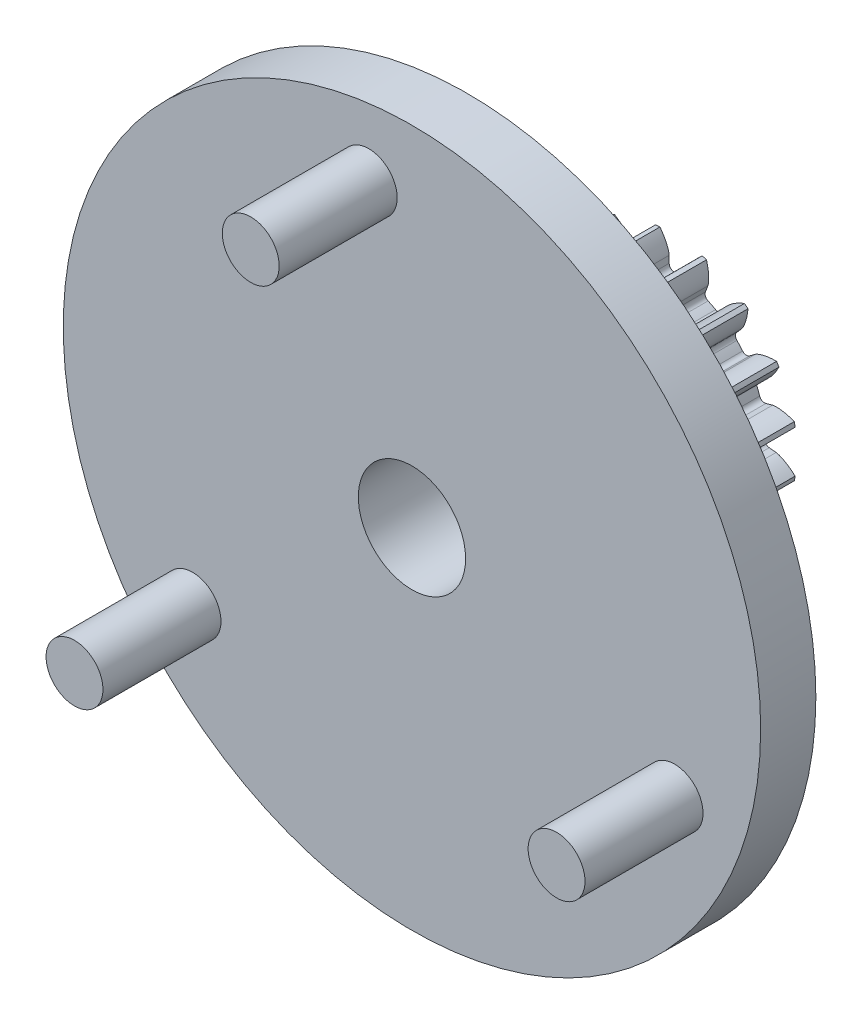
SolidWorks part; units mm, degrees
ref_plane "Front Plane" through (0, 0, 0) normal (0, 0, 1) x (1, 0, 0)
ref_plane "Top Plane" through (0, 0, 0) normal (0, 1, 0) x (1, 0, 0)
ref_plane "Right Plane" through (0, 0, 0) normal (1, 0, 0) x (0, 0, -1)
ref_axis "Gear Axis" through (0, 0, -0.2501) along (0, 0, 1)
sketch "Blank Sketch" plane through (0, 0, 0) normal (0, 0, 1) x (1, 0, 0)
  circle A0 centre (0, 0) radius 11.875
  dimension "OD" = 23.75
extrude "Blank" add sketch "Blank Sketch" along normal blind 5
sketch "Tooth Space Sketch" plane through (0, 0, 0) normal (0, 0, 1) x (1, 0, 0)
  line L0 (9.9391, 0.9485) -> (9.2957, 0.8871)
  line L1 (9.9391, -0.9485) -> (9.2957, -0.8871)
  line L2 (12.7424, 3.1457) -> (12.7424, -3.1457)
  arc A0 (9.2957, 0.8871) -> (8.8663, 0.3932) centre (9.3408, 0.4142) ccw
  arc A1 (8.8663, -0.3932) -> (9.2957, -0.8871) centre (9.3408, -0.4142) ccw
  arc A2 (8.8663, -0.3932) -> (8.8663, 0.3932) centre (0, 0) ccw
  spline S0 degree 4 poles (9.9391, 0.9485) (9.9444, 0.9491) (9.9594, 0.9511) (9.9875, 0.9561) (10.033, 0.9658) (10.0906, 0.9807) (10.1644, 1.0027) (10.2505, 1.0321) (10.344, 1.0681) (10.4445, 1.1112) (10.5435, 1.1577) (10.6412, 1.2072) (10.7373, 1.2593) (10.8523, 1.3258) (10.9883, 1.4101) (11.1441, 1.5151) (11.3169, 1.6419) (11.4885, 1.7791) (11.6537, 1.9206) (11.816, 2.0708) (11.9698, 2.2212) (12.1246, 2.3846) (12.2649, 2.5391) (12.4162, 2.7198) (12.5367, 2.8679) (12.6891, 3.071) (12.7772, 3.1933) (12.878, 3.3391) (12.9216, 3.4052) (12.9484, 3.4459) knots 0 0 0 0 0 0.005377 0.015084 0.028532 0.04661 0.064855 0.092111 0.119476 0.146842 0.174209 0.201575 0.228941 0.256307 0.307035 0.361767 0.4165 0.471232 0.525964 0.580697 0.635429 0.690161 0.744894 0.799626 0.854358 0.909091 0.954545 1 1 1 1 1 construction
  spline S1 degree 4 poles (9.9391, 0.9485) (9.9444, 0.9491) (9.9594, 0.9511) (9.9875, 0.9561) (10.033, 0.9658) (10.0906, 0.9807) (10.1644, 1.0027) (10.2505, 1.0321) (10.344, 1.0681) (10.4445, 1.1112) (10.5435, 1.1577) (10.6412, 1.2072) (10.7373, 1.2593) (10.8523, 1.3258) (10.9883, 1.4101) (11.1441, 1.5151) (11.3169, 1.6419) (11.4885, 1.7791) (11.6537, 1.9206) (11.816, 2.0708) (11.9698, 2.2212) (12.1246, 2.3846) (12.2649, 2.5391) (12.4162, 2.7198) (12.5367, 2.8679) (12.6561, 3.027) (12.7135, 3.1053) (12.7424, 3.1457) knots 0 0 0 0 0 0.005377 0.015084 0.028532 0.04661 0.064855 0.092111 0.119476 0.146842 0.174209 0.201575 0.228941 0.256307 0.307035 0.361767 0.4165 0.471232 0.525964 0.580697 0.635429 0.690161 0.744894 0.799626 0.854358 0.909091 0.909091 0.909091 0.909091 0.909091
  spline S2 degree 4 poles (9.9391, -0.9485) (9.9444, -0.9491) (9.9594, -0.9511) (9.9875, -0.9561) (10.033, -0.9658) (10.0906, -0.9807) (10.1644, -1.0027) (10.2505, -1.0321) (10.344, -1.0681) (10.4445, -1.1112) (10.5435, -1.1577) (10.6412, -1.2072) (10.7373, -1.2593) (10.8523, -1.3258) (10.9883, -1.4101) (11.1441, -1.5151) (11.3169, -1.6419) (11.4885, -1.7791) (11.6537, -1.9206) (11.816, -2.0708) (11.9698, -2.2212) (12.1246, -2.3846) (12.2649, -2.5391) (12.4162, -2.7198) (12.5367, -2.8679) (12.6891, -3.071) (12.7772, -3.1933) (12.878, -3.3391) (12.9216, -3.4052) (12.9484, -3.4459) knots 0 0 0 0 0 0.005377 0.015084 0.028532 0.04661 0.064855 0.092111 0.119476 0.146842 0.174209 0.201575 0.228941 0.256307 0.307035 0.361767 0.4165 0.471232 0.525964 0.580697 0.635429 0.690161 0.744894 0.799626 0.854358 0.909091 0.954545 1 1 1 1 1 construction
  spline S3 degree 4 poles (9.9391, -0.9485) (9.9444, -0.9491) (9.9594, -0.9511) (9.9875, -0.9561) (10.033, -0.9658) (10.0906, -0.9807) (10.1644, -1.0027) (10.2505, -1.0321) (10.344, -1.0681) (10.4445, -1.1112) (10.5435, -1.1577) (10.6412, -1.2072) (10.7373, -1.2593) (10.8523, -1.3258) (10.9883, -1.4101) (11.1441, -1.5151) (11.3169, -1.6419) (11.4885, -1.7791) (11.6537, -1.9206) (11.816, -2.0708) (11.9698, -2.2212) (12.1246, -2.3846) (12.2649, -2.5391) (12.4162, -2.7198) (12.5367, -2.8679) (12.6561, -3.027) (12.7135, -3.1053) (12.7424, -3.1457) knots 0 0 0 0 0 0.005377 0.015084 0.028532 0.04661 0.064855 0.092111 0.119476 0.146842 0.174209 0.201575 0.228941 0.256307 0.307035 0.361767 0.4165 0.471232 0.525964 0.580697 0.635429 0.690161 0.744894 0.799626 0.854358 0.909091 0.909091 0.909091 0.909091 0.909091
  dimension "Root" = 8.875
  dimension "Fillet" = 0.475
extrude "Tooth Space" cut sketch "Tooth Space Sketch" against normal through all both and the other way through all both
pattern_circular "Teeth" count 17 over 360 about axis through (0, 0, -0.2501) along (0, 0, 1) of "Tooth Space"
sketch "Bore Sketch" plane through (0, 0, 0) normal (0, 0, 1) x (1, 0, 0)
  circle A0 centre (0, 0) radius 5
  dimension "Bore" = 10
extrude "Bore" cut sketch "Bore Sketch" against normal through all both and the other way through all both
ref_plane "Plane1" through (0, 0, 24) normal (0, 0, 1) x (1, 0, 0)
sketch "Sketch1" plane through (0, 0, 24) normal (0, 0, 1) x (1, 0, 0)
  line L0 (0, 0) -> (-4.0265, 25.9393) construction
  line L1 (0, 0) -> (0, 26.25) construction
  circle A0 centre (0, 0) radius 26.25 construction
  circle A5 centre (-4.0265, 25.9393) radius 2.65
  circle A6 centre (0, 0) radius 5
  circle A7 centre (0, 0) radius 32.5
  point P15 (0, 0)
  dimension "D1" = 52.5
  dimension "D3" = 5.3
  dimension "D4" = 10
  dimension "D5" = 65
  dimension "D2" = 8.824
extrude "Boss-Extrude1" add sketch "Sketch1" against normal blind 5 separate body contours A7 A5 A6 | A5 region at (-4.0265, 25.9393, 24) region at (-31.5808, 0, 24)
sketch "Sketch3" plane through (0, 0, 19) normal (0, 0, -1) x (-1, 0, 0)
  circle A1 centre (0, 0) radius 5
  circle A2 centre (0, 0) radius 8.75
  circle A3 centre (0, 0) radius 5 construction
  dimension "D1" = 17.5
extrude "Boss-Extrude2" add sketch "Sketch3" along normal up to surface (14 mm away) up to face at (5, 0, 5)
chamfer "Chamfer2" distance 24 angle 30 1 edges at (-8.75, 0, 19) first distance on face at (-8.75, 0, 19)
extrude "Boss-Extrude3" add sketch "Sketch1<5>" along normal blind 11 contours A5
sketch "Sketch1<5>" plane through (0, 0, 24) normal (0, 0, 1) x (1, 0, 0) same geometry as "Sketch1"
pattern_circular "CirPattern1" count 3 over 360 about axis through (0, 0, 19) along (0, 0, 1) of "Boss-Extrude3"
equation "\"No. of Teeth\"= 17"
equation "\"Module\"= 1.25"
equation "\"Bore Diameter\"= 10"
equation "\"Pressure Angle\"= 20"
equation "\"Outer Diameter\"= ( \"No. of Teeth\" + 2 ) * \"Module\""
equation "\"Pitch Diameter\"= \"No. of Teeth\" * \"Module\""
equation "\"Backlash\"= 0.3 * \"Module\""
equation "\"Arc Length\"= ( ( \"Module\" * pi ) / 2 + \"Backlash\" )"
equation "\"Fillet Radius\"= 0.38 * \"Module\""
equation "\"Tooth Depth\"= IIF ( \"Module\" <= 1.25 , \"Module\" * 2.4 , \"Module\" * 2.25 )"
equation "\"Face Width\"= 5"
equation "\"Root Diameter\"= \"Outer Diameter\" - 2 * \"Tooth Depth\""
equation "\"Base Diameter\"= \"Pitch Diameter\" * cos ( \"Pressure Angle\" )"
equation "\"Base Radius\"= \"Base Diameter\" / 2"
equation "\"Tooth Thickness\"= \"Module\" * pi - \"Arc Length\""
equation "\"Half Space Angle\"= ( \"Arc Length\" / \"Pitch Diameter\" ) * 180 / pi"
equation "\"Involute Fn\"= tan ( \"Pressure Angle\" ) - \"Pressure Angle\" * pi / 180"
equation "\"Flank Offset\"= \"Arc Length\" / \"Pitch Diameter\" - \"Involute Fn\""
equation "\"Tip Cap Diameter\"= \"Outer Diameter\" + 2 * \"Module\""
equation "\"Flank Start Diameter\"= IIF ( \"Base Diameter\" >= ( \"Root Diameter\" + 3 * \"Fillet Radius\" ) , \"Base Diameter\" , \"Root Diameter\" + 3 * \"Fillet Radius\" )"
equation "\"Involute t1\"= ( abs ( ( \"Flank Start Diameter\" / \"Base Diameter\" ) ^ 2 - 1 ) ) ^ 0.5"
equation "\"Involute t2\"= ( abs ( ( \"Tip Cap Diameter\" / \"Base Diameter\" ) ^ 2 - 1 ) ) ^ 0.5"
equation "\"Flank Arc Radius\"= ( \"Pitch Diameter\" / 2 ) * sin ( \"Pressure Angle\" )"
equation "\"Flank Centre Angle\"= \"Half Space Angle\" + \"Pressure Angle\""
equation "\"OD@Blank Sketch\"= \"Outer Diameter\""
equation "\"Width@Blank\"= \"Face Width\""
equation "\"Root@Tooth Space Sketch\"= \"Root Diameter\" / 2"
equation "\"Fillet@Tooth Space Sketch\"= \"Fillet Radius\""
equation "\"Count@Teeth\"= \"No. of Teeth\""
equation "\"Bore@Bore Sketch\"= \"Bore Diameter\""
